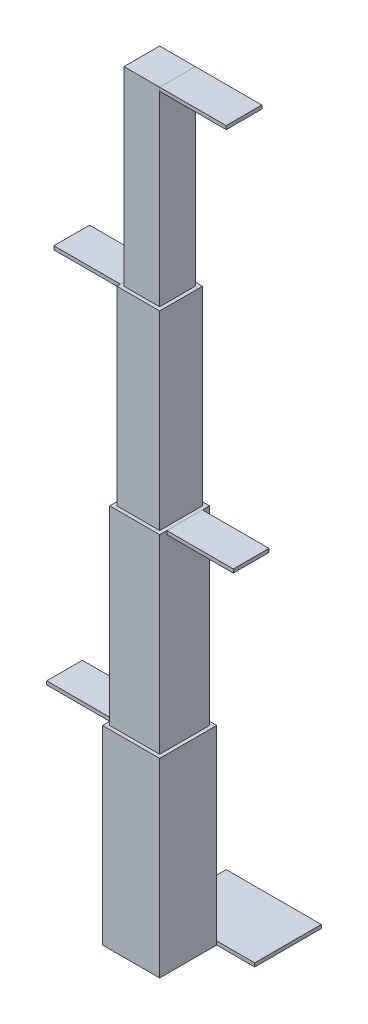
SolidWorks part; units mm, degrees
ref_plane "Front Plane" through (0, 0, 0) normal (0, 0, 1) x (1, 0, 0)
ref_plane "Top Plane" through (0, 0, 0) normal (0, 1, 0) x (1, 0, 0)
ref_plane "Right Plane" through (0, 0, 0) normal (1, 0, 0) x (0, 0, -1)
sketch "Sketch1" plane through (0, 0, 0) normal (0, 1, 0) x (1, 0, 0)
  line L0 (9.525, 9.525) -> (9.525, 142.875)
  line L1 (0, 0) -> (152.4, 0)
  line L2 (0, 0) -> (0, 152.4)
  line L3 (0, 152.4) -> (152.4, 152.4)
  line L4 (152.4, 0) -> (152.4, 152.4)
  line L5 (9.525, 142.875) -> (142.875, 142.875)
  line L6 (142.875, 9.525) -> (142.875, 142.875)
  line L7 (9.525, 9.525) -> (142.875, 9.525)
  line L8 (19.05, 19.05) -> (19.05, 133.35)
  line L9 (19.05, 133.35) -> (133.35, 133.35)
  line L10 (133.35, 19.05) -> (133.35, 133.35)
  line L11 (19.05, 19.05) -> (133.35, 19.05)
  line L12 (28.575, 28.575) -> (28.575, 123.825)
  line L13 (28.575, 123.825) -> (123.825, 123.825)
  line L14 (123.825, 28.575) -> (123.825, 123.825)
  line L15 (28.575, 28.575) -> (123.825, 28.575)
  dimension "D1" = 152.4
  dimension "D2" = 9.525
  dimension "D3" = 9.525
  dimension "D4" = 9.525
extrude "Boss-Extrude4" add sketch "Sketch1" along normal blind 2032 contours L12 L13 L14 L15
extrude "Boss-Extrude5" add sketch "Sketch1<8>" along normal blind 1524 separate body contours L11 L10 L9 L8
sketch "Sketch1<8>" plane through (0, 0, 0) normal (0, 1, 0) x (1, 0, 0) same geometry as "Sketch1"
extrude "Boss-Extrude6" add sketch "Sketch1<9>" along normal blind 1016 separate body contours L7 L6 L5 L0
sketch "Sketch1<9>" plane through (0, 0, 0) normal (0, 1, 0) x (1, 0, 0) same geometry as "Sketch1"
extrude "Boss-Extrude7" add sketch "Sketch1<10>" along normal blind 508 separate body contours L1 L4 L3 L2
sketch "Sketch1<10>" plane through (0, 0, 0) normal (0, 1, 0) x (1, 0, 0) same geometry as "Sketch1"
sketch "Sketch2" plane through (123.825, 0, 0) normal (1, 0, 0) x (0, 0, -1)
  line L0 (123.825, 2032) -> (123.825, 0) construction
  line L1 (28.575, 2032) -> (123.825, 2032)
  line L2 (28.575, 2032) -> (28.575, 2022.475)
  line L3 (28.575, 2022.475) -> (123.825, 2022.475)
  line L4 (123.825, 2032) -> (123.825, 2022.475)
  dimension "D1" = 9.525
extrude "Boss-Extrude8" add sketch "Sketch2" along normal blind 177.8 separate body
sketch "Sketch3" plane through (19.05, 0, 0) normal (-1, 0, 0) x (0, 0, 1)
  line L0 (-19.05, 1524) -> (-133.35, 1524) construction
  line L1 (-123.825, 1524) -> (-28.575, 1524)
  line L2 (-123.825, 1524) -> (-123.825, 1514.475)
  line L3 (-123.825, 1514.475) -> (-28.575, 1514.475)
  line L4 (-28.575, 1524) -> (-28.575, 1514.475)
  line L5 (-123.825, 2032) -> (-123.825, 0) construction
  line L6 (-28.575, 2032) -> (-28.575, 0) construction
  dimension "D1" = 9.525
extrude "Boss-Extrude9" add sketch "Sketch3" along normal blind 177.8 separate body
sketch "Sketch5" plane through (142.875, 0, 0) normal (1, 0, 0) x (0, 0, -1)
  line L0 (28.575, 2032) -> (28.575, 0) construction
  line L1 (28.575, 1016) -> (123.825, 1016)
  line L2 (28.575, 1016) -> (28.575, 1006.475)
  line L3 (28.575, 1006.475) -> (123.825, 1006.475)
  line L4 (123.825, 1016) -> (123.825, 1006.475)
  line L5 (123.825, 2032) -> (123.825, 0) construction
  dimension "D1" = 9.525
extrude "Boss-Extrude10" add sketch "Sketch5" along normal blind 177.8 separate body
sketch "Sketch6" plane through (0, 0, 0) normal (-1, 0, 0) x (0, 0, 1)
  line L0 (0, 508) -> (-152.4, 508) construction
  line L1 (-123.825, 508) -> (-28.575, 508)
  line L2 (-123.825, 508) -> (-123.825, 498.475)
  line L3 (-123.825, 498.475) -> (-28.575, 498.475)
  line L4 (-28.575, 508) -> (-28.575, 498.475)
  line L5 (-123.825, 2032) -> (-123.825, 0) construction
  line L6 (-28.575, 2032) -> (-28.575, 0) construction
  dimension "D1" = 9.525
extrude "Boss-Extrude11" add sketch "Sketch6" along normal blind 177.8 separate body
sketch "Sketch7" plane through (0, 0, -152.4) normal (0, 0, -1) x (-1, 0, 0)
  line L1 (0, 0) -> (-254, 0)
  line L2 (0, 0) -> (0, 9.525)
  line L3 (0, 9.525) -> (-254, 9.525)
  line L4 (-254, 0) -> (-254, 9.525)
  dimension "D1" = 254
  dimension "D2" = 9.525
extrude "Boss-Extrude12" add sketch "Sketch7" along normal blind 177.8 separate body contours L3 L4 L1 L2
